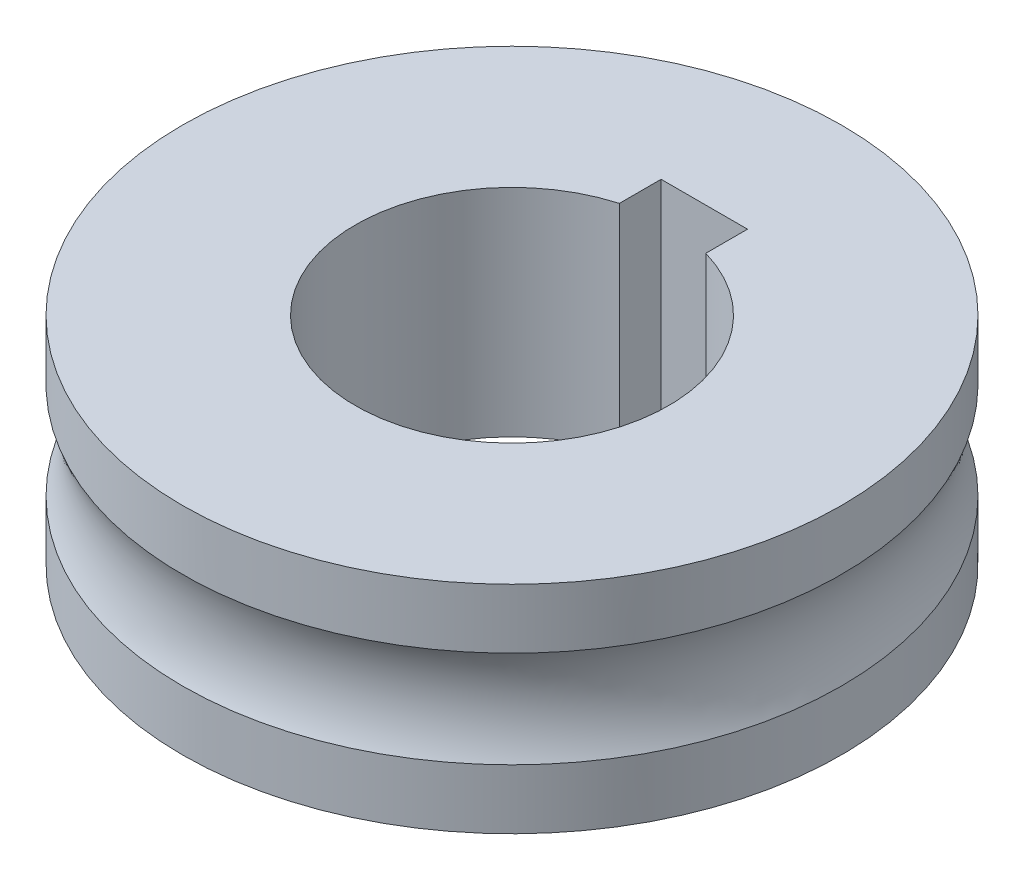
SolidWorks part; units mm, degrees
ref_plane "前视基准面" through (0, 0, 0) normal (0, 0, 1) x (1, 0, 0)
ref_plane "上视基准面" through (0, 0, 0) normal (0, 1, 0) x (1, 0, 0)
ref_plane "右视基准面" through (0, 0, 0) normal (1, 0, 0) x (0, 0, -1)
other "Configuration Table"
sketch "草图1" plane through (0, 0, 0) normal (0, 1, 0) x (1, 0, 0)
  line L0 (0, 14.5) -> (0, 25.7655) construction
  line L1 (-4, 17.8) -> (-4, 13.9374)
  line L2 (-4, 17.8) -> (4, 17.8)
  line L3 (4, 17.8) -> (4, 13.9374)
  circle A0 centre (0, 0) radius 30.5
  arc A1 (-4, 13.9374) -> (4, 13.9374) centre (0, 0) ccw
  dimension "D1" = 61
  dimension "D2" = 29
  dimension "D3" = 8
  dimension "D4" = 32.3
extrude "凸台-拉伸1" add sketch "草图1" along normal blind 20
sketch "草图2" plane through (0, 0, 0) normal (0, 0, 1) x (1, 0, 0)
  line L2 (-30.5, 10) -> (-40, 10) construction
  line L3 (-30.5, 20) -> (-30.5, 0) construction
  line L4 (0, 0) -> (0, 20) construction
  line L5 (30.5, 20) -> (-30.5, 20) construction
  circle A0 centre (-40, 10) radius 10.5
  dimension "D2" = 21
  dimension "D1" = 40
revolve "切除-旋转1" cut sketch "草图2" angle 360 about L4
